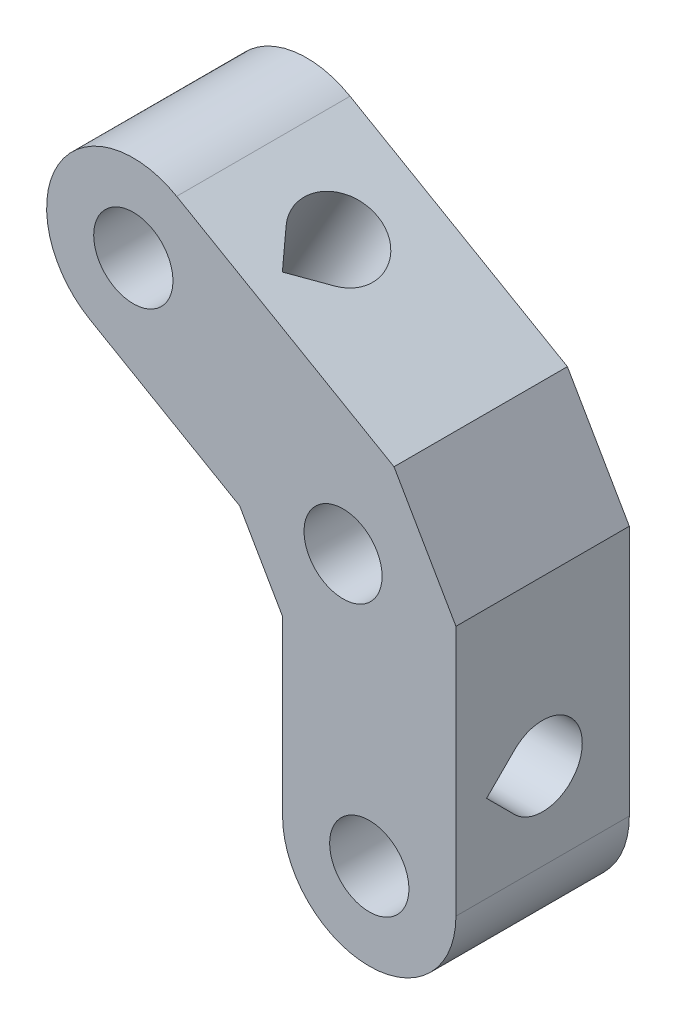
SolidWorks part; units mm, degrees
ref_plane "Front Plane" through (0, 0, 0) normal (0, 0, 1) x (1, 0, 0)
ref_plane "Top Plane" through (0, 0, 0) normal (0, 1, 0) x (1, 0, 0)
ref_plane "Right Plane" through (0, 0, 0) normal (1, 0, 0) x (0, 0, -1)
ref_plane "Plane4" through (0, 0, 14) normal (0, 0, 1) x (1, 0, 0)
sketch "Sketch1" plane through (0, 0, 14) normal (0, 0, 1) x (1, 0, 0)
  line L0 (7, 0) -> (7, 20.2679)
  line L1 (7, 20.2679) -> (2, 28.9282)
  line L2 (2, 28.9282) -> (-15.5526, 39.0622)
  line L3 (-22.5526, 26.9378) -> (-10.4641, 19.9585)
  line L4 (-10.4641, 19.9585) -> (-7, 13.9585)
  line L5 (-7, 13.9585) -> (-7, 0)
  line L6 (-8.7321, 16.9585) -> (4.5, 24.5981) construction
  arc A0 (-15.5526, 39.0622) -> (-22.5526, 26.9378) centre (-19.0526, 33) ccw
  arc A1 (-7, 0) -> (7, 0) centre (0, 0) ccw
  dimension "D2" = 7
  dimension "D1" = 120
  dimension "D3" = 150
  dimension "D4" = 10
  dimension "D5" = 38.1051
extrude "Boss-Extrude1" add sketch "Sketch1" against normal blind 14
hole_wizard "Hole1" positions "Sketch5" profile "Sketch4" legacy
sketch "Sketch5" plane through (0, 0, 0) normal (0, 0, -1) x (-1, 0, 0)
  point P0 (0, 0)
sketch "Sketch4" plane through (0, 0, 0) normal (1, 0, 0) x (0, 1, 0)
  line L0 (0, 0) -> (0, 14)
  line L1 (0, 14) -> (3.2, 14)
  line L2 (3.2, 14) -> (3.2, 0)
  line L3 (3.2, 0) -> (0, 0)
  line L4 (0, 110) -> (0, -10) construction
  dimension "Diameter" = 6.4
  dimension "Depth" = 14
hole_wizard "Hole2" positions "Sketch7" profile "Sketch6" legacy
sketch "Sketch7" plane through (0, 0, 0) normal (0, 0, -1) x (-1, 0, 0)
  line L0 (0, 0) -> (19.0525, 32.9999) construction
  line L2 (0, 0) -> (22.3725, 0) construction
  point P0 (19.0525, 32.9999)
  dimension "D1" = 38.105
  dimension "D2" = 60
sketch "Sketch6" plane through (-19.0525, 32.9999, 0) normal (1, 0, 0) x (0, 1, 0)
  line L0 (0, 0) -> (0, 14)
  line L1 (0, 14) -> (3.2, 14)
  line L2 (3.2, 14) -> (3.2, 0)
  line L3 (3.2, 0) -> (0, 0)
  line L4 (0, 110) -> (0, -10) construction
  dimension "Diameter" = 6.4
  dimension "Depth" = 14
ref_axis "Axis1" through (-19.0525, 32.9999, 14) along (0, 0, -1)
sketch "Sketch2" plane through (6.0263, 10.4378, 0) normal (-0.5, -0.866, 0) x (0.866, -0.5, 0)
  line L0 (-25.9999, 11.5255) -> (-28.2626, 9.2627)
  line L1 (-23.7372, 9.2627) -> (-25.9999, 11.5255)
  line L2 (-32.9999, 14) -> (-32.9999, 0) construction
  line L3 (-19.0415, 7) -> (-31.5924, 7) construction
  line L4 (-19.0415, 0) -> (-19.0415, 14) construction
  arc A0 (-28.2626, 9.2627) -> (-23.7372, 9.2627) centre (-25.9999, 7) ccw
  dimension "D1" = 7
  dimension "D2" = 3.2
  dimension "D3" = 45
extrude "Cut-Extrude1" cut sketch "Sketch2" against normal through all
sketch "Sketch3" plane through (-7, 0, 0) normal (-1, 0, 0) x (0, 0, 1)
  line L0 (9.2627, 4.7373) -> (11.5255, 7)
  line L1 (11.5255, 7) -> (9.2627, 9.2627)
  line L2 (7, 0) -> (7, 13.9585) construction
  line L3 (0, 0) -> (14, 0) construction
  line L4 (0, 13.9585) -> (14, 13.9585) construction
  arc A0 (9.2627, 9.2627) -> (9.2627, 4.7373) centre (7, 7) ccw
  dimension "D2" = 3.2
  dimension "D1" = 7
  dimension "D3" = 45
extrude "Cut-Extrude2" cut sketch "Sketch3" against normal through all
sketch "Sketch8" plane through (0, 0, 14) normal (0, 0, 1) x (1, 0, 0)
  line L0 (-8.7321, 16.9585) -> (4.5, 24.5981) construction
  line L1 (-10.4641, 19.9585) -> (-7, 13.9585) construction
  line L2 (7, 20.2679) -> (2, 28.9282) construction
  circle A0 centre (-2.116, 20.7783) radius 3.15
  dimension "D1" = 6.3
extrude "Cut-Extrude3" cut sketch "Sketch8" against normal through all
